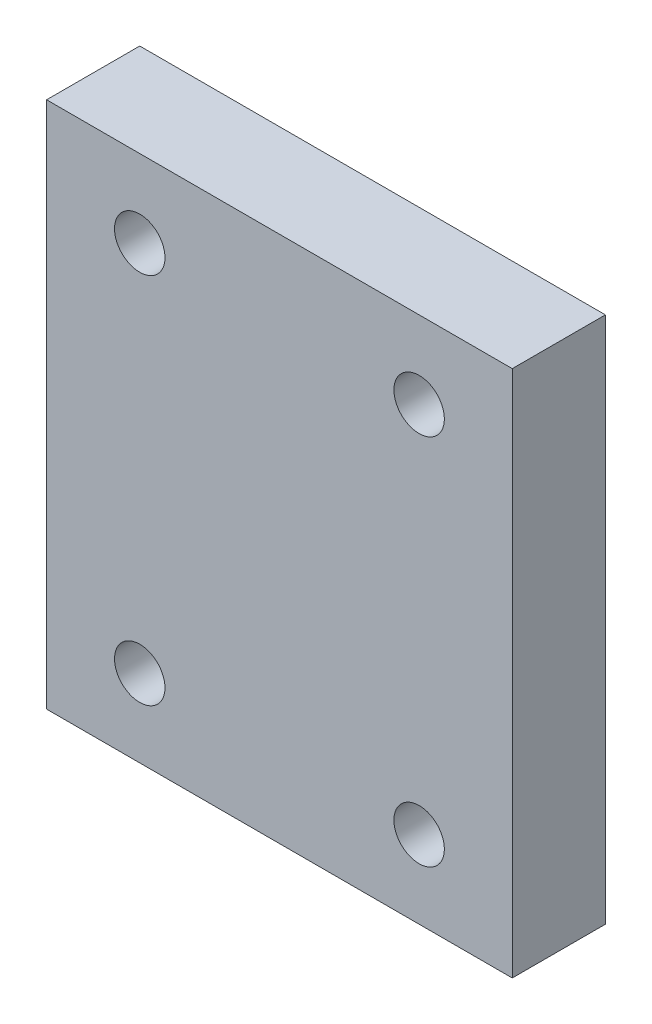
SolidWorks part; units mm, degrees
ref_plane "Front Plane" through (0, 0, 0) normal (0, 0, 1) x (1, 0, 0)
ref_plane "Top Plane" through (0, 0, 0) normal (0, 1, 0) x (1, 0, 0)
ref_plane "Right Plane" through (0, 0, 0) normal (1, 0, 0) x (0, 0, -1)
sketch "Sketch1" plane through (0, 0, 0) normal (0, 0, 1) x (1, 0, 0)
  line L1 (-9, -12) -> (9, -12) construction
  line L2 (-9, -12) -> (-9, 12) construction
  line L3 (-9, 12) -> (9, 12) construction
  line L4 (9, -12) -> (9, 12) construction
  line L5 (-9, -12) -> (9, 12) construction
  line L6 (-9, 12) -> (9, -12) construction
  line L7 (-15, 17) -> (15, 17)
  line L8 (-15, 17) -> (-15, -17)
  line L9 (-15, -17) -> (15, -17)
  line L10 (15, 17) -> (15, -17)
  line L11 (-15, 17) -> (15, -17) construction
  line L12 (-15, -17) -> (15, 17) construction
  circle A0 centre (-9, 12) radius 1.625
  circle A1 centre (9, 12) radius 1.625
  circle A2 centre (-9, -12) radius 1.625
  circle A3 centre (9, -12) radius 1.625
  point P0 (0, 0)
  point P6 (0, 0)
  dimension "D5" = 3.25
  dimension "D1" = 30
  dimension "D2" = 34
  dimension "D3" = 5
  dimension "D4" = 6
extrude "Boss-Extrude1" add sketch "Sketch1" along normal blind 6
